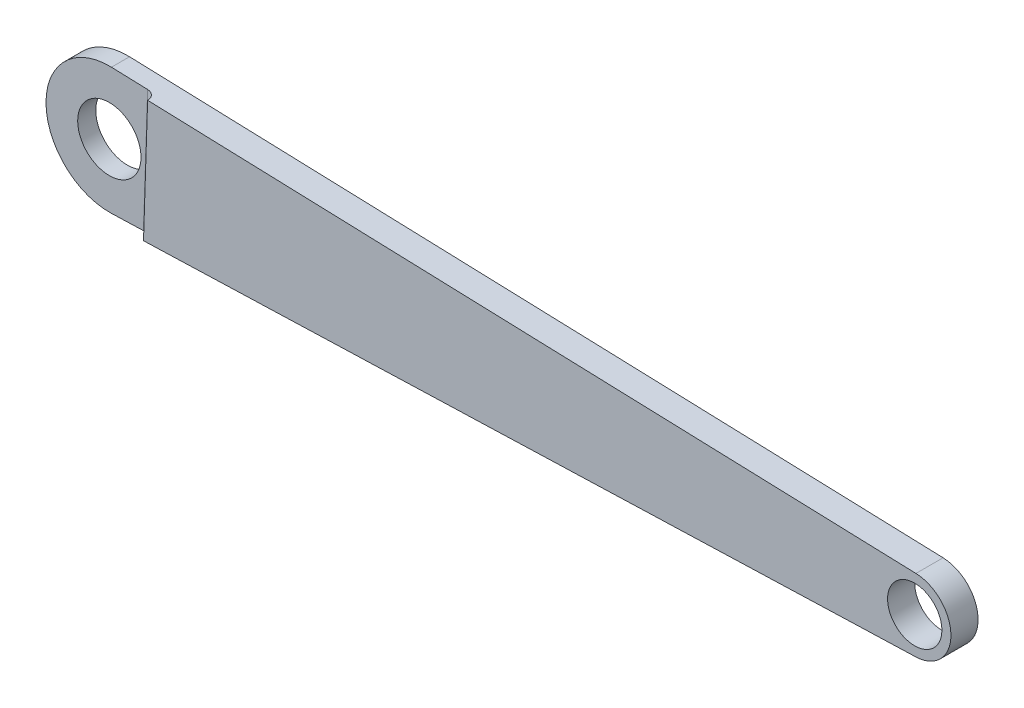
SolidWorks part; units mm, degrees
ref_plane "Front Plane" through (0, 0, 0) normal (0, 0, 1) x (1, 0, 0)
ref_plane "Top Plane" through (0, 0, 0) normal (0, 1, 0) x (1, 0, 0)
ref_plane "Right Plane" through (0, 0, 0) normal (1, 0, 0) x (0, 0, -1)
sketch "Sketch1" plane through (0, 0, 0) normal (0, 0, 1) x (1, 0, 0)
  line L0 (-1143, 0) -> (1143, 0) construction
  line L1 (-1137.0733, 177.7012) -> (1146.3867, 101.5435)
  line L2 (-1137.0733, -177.7012) -> (1146.3867, -101.5435)
  arc A0 (-1137.0733, 177.7012) -> (-1137.0733, -177.7012) centre (-1143, 0) ccw
  arc A1 (1146.3867, -101.5435) -> (1146.3867, 101.5435) centre (1143, 0) ccw
  circle A2 centre (-1143, 0) radius 88.9
  circle A3 centre (1143, 0) radius 76.2
  point P4 (0, 0)
  dimension "D2" = 355.6
  dimension "D3" = 203.2
  dimension "D4" = 177.8
  dimension "D5" = 152.4
  dimension "D1" = 1143
  dimension "D6" = 1143
extrude "Boss-Extrude1" add sketch "Sketch1" along normal mid plane 76.2
sketch "Sketch2" plane through (4.6567, 139.6224, 0) normal (0.0333, 0.9994, 0) x (0.9994, -0.0333, 0)
  line L0 (-1320.1648, 38.1) -> (-1015.3648, 38.1) construction
  line L1 (1142.3648, 38.1) -> (-1142.3648, 38.1) construction
  line L2 (-1320.1648, -38.1) -> (-1320.1648, -12.7)
  line L3 (-1320.1648, 38.1) -> (-1320.1648, -38.1) construction
  line L4 (-1320.1648, -12.7) -> (-1015.3648, -12.7)
  line L5 (-1015.3648, -12.7) -> (-1015.3648, -38.1)
  line L6 (1142.3648, -38.1) -> (-1142.3648, -38.1) construction
  line L7 (-1015.3648, -38.1) -> (-1320.1648, -38.1)
  dimension "D1" = 304.8
  dimension "D2" = 25.4
  dimension "D3" = 304.8
extrude "Cut-Extrude1" cut sketch "Sketch2" against normal through all both and the other way through all
fillet "Fillet1" radius 25.4 1 edges at (-1015.9358, -0.1932, 12.7)
